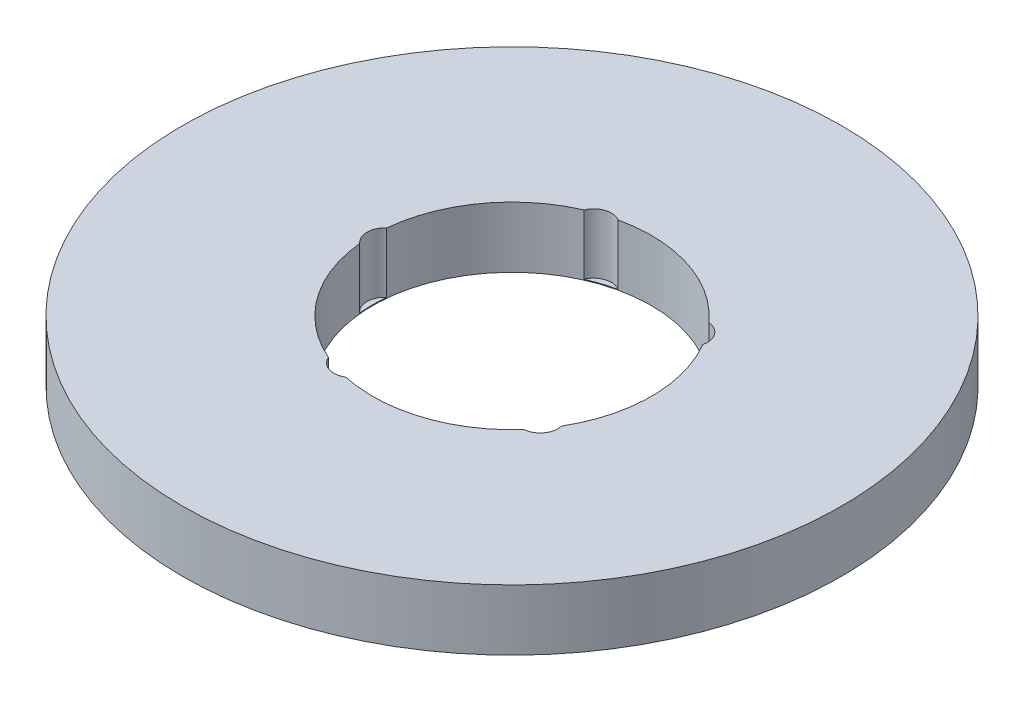
SolidWorks part; units mm, degrees
ref_plane "Front Plane" through (0, 0, 0) normal (0, 0, 1) x (1, 0, 0)
ref_plane "Top Plane" through (0, 0, 0) normal (0, 1, 0) x (1, 0, 0)
ref_plane "Right Plane" through (0, 0, 0) normal (1, 0, 0) x (0, 0, -1)
sketch "Sketch1" plane through (0, 0, 0) normal (0, 1, 0) x (1, 0, 0)
  circle A0 centre (0, 0) radius 65
  dimension "FLANGE_OD" = 130
extrude "Boss-Extrude1" add sketch "Sketch1" along normal blind 12
sketch "Sketch2" plane through (0, 0, 0) normal (0, 1, 0) x (1, 0, 0)
  circle A0 centre (0, 0) radius 27.5
  dimension "BORE_D" = 55
extrude "Cut-Extrude1" cut sketch "Sketch2" along normal through all
sketch "Sketch3" plane through (0, 12, 0) normal (0, 1, 0) x (1, 0, 0)
  circle A0 centre (0, 0) radius 25.0942 construction
  circle A1 centre (-25.0942, 0) radius 3.5046
  dimension "BOLT_D" = 7.0092
  dimension "BOLT_PCD" = 50.1884
extrude "Cut-Extrude2" cut sketch "Sketch3" against normal blind 11.8456
pattern_circular "CirPattern1" count 5 over 360 about axis through (0, 0, 0) along (0, 1, 0) of "Cut-Extrude2"
